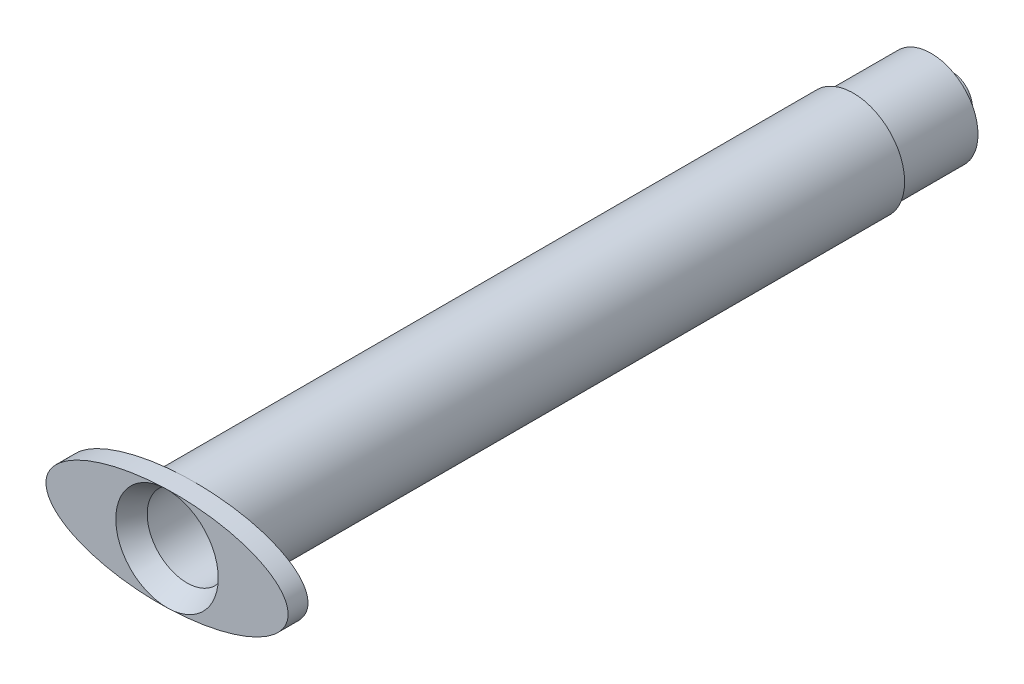
SolidWorks part; units mm, degrees
ref_plane "Front Plane" through (0, 0, 0) normal (0, 0, 1) x (1, 0, 0)
ref_plane "Top Plane" through (0, 0, 0) normal (0, 1, 0) x (1, 0, 0)
ref_plane "Right Plane" through (0, 0, 0) normal (1, 0, 0) x (0, 0, -1)
sketch "Sketch1" plane through (0, 0, 0) normal (0, 0, 1) x (1, 0, 0)
  circle A0 centre (0, 0) radius 4.1
  circle A1 centre (0, 0) radius 5.17
extrude "Boss-Extrude1" add sketch "Sketch1" along normal blind 67.25
sketch "Sketch2" plane through (0, 0, 67.25) normal (0, 0, 1) x (1, 0, 0)
  circle A0 centre (0, 0) radius 5.17 construction
  ellipse E0 centre (0, 0) end of major axis (-12.2124, -0.4308) minor radius 5.17
extrude "Boss-Extrude2" add sketch "Sketch2" along normal blind 2.01
sketch "Sketch3" plane through (0, 0, 69.26) normal (0, 0, 1) x (1, 0, 0)
  circle A0 centre (0, 0) radius 5.17
extrude "Cut-Extrude1" cut sketch "Sketch3" against normal blind 2.01 draft 30
sketch "Sketch4" plane through (0, 0, 0) normal (0, 0, -1) x (-1, 0, 0)
  circle A0 centre (0, 0) radius 0.795
  circle A1 centre (0, 0) radius 2.06
  point P4 (0, 0)
extrude "Boss-Extrude3" add sketch "Sketch4" along normal blind 9.95 separate body
sketch "Sketch5" plane through (0, 0, 0) normal (0, 0, -1) x (-1, 0, 0)
  circle A0 centre (0, 0) radius 4.0953
  dimension "D1" = 8.1905
extrude "Boss-Extrude4" add sketch "Sketch5" along normal blind 1.15
sketch "Sketch7" plane through (0, 0, -9.95) normal (0, 0, -1) x (-1, 0, 0)
  circle A0 centre (0, 0) radius 0.795
extrude "Cut-Extrude2" cut sketch "Sketch7" against normal through all
sketch "Sketch8" plane through (0, 0, 0) normal (0, 0, -1) x (-1, 0, 0)
sketch "Sketch9" plane through (0, 0, 0) normal (0, 0, -1) x (-1, 0, 0)
  circle A0 centre (0, 0) radius 4.11
  circle A1 centre (0, 0) radius 4.725
extrude "Boss-Extrude6" add sketch "Sketch9" along normal blind 7.85
